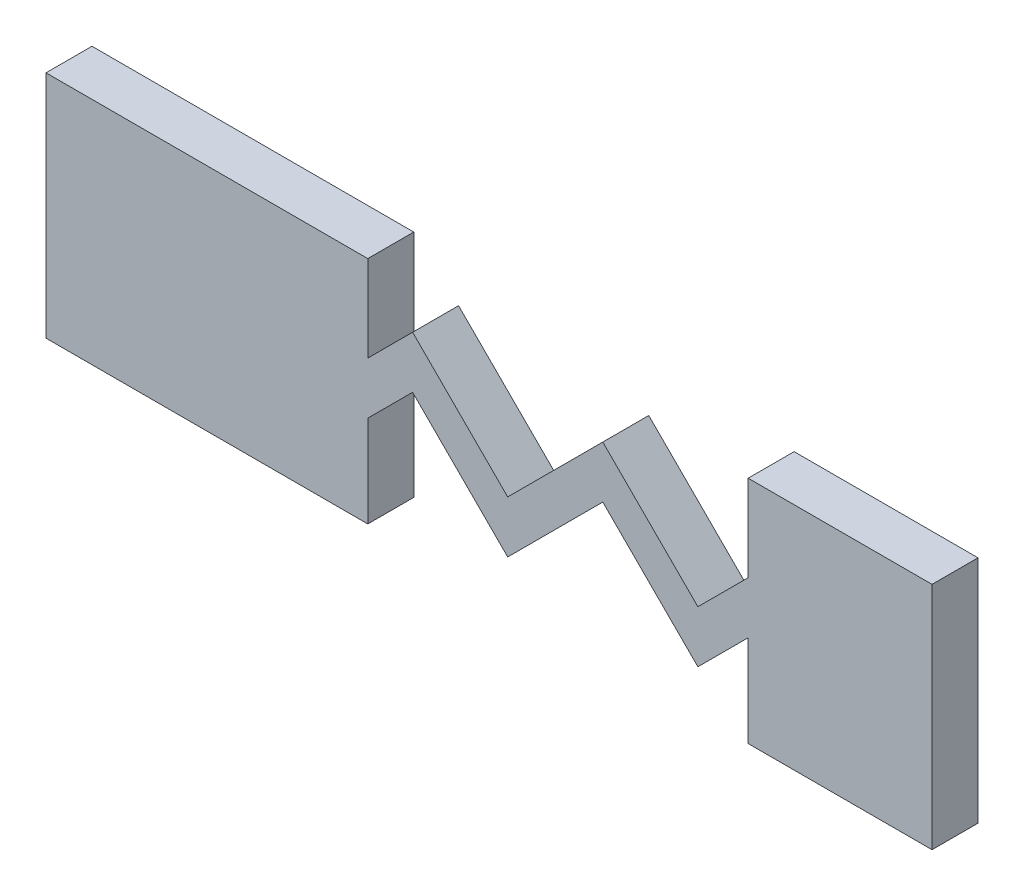
SolidWorks part; units mm, degrees
ref_plane "Front Plane" through (0, 0, 0) normal (0, 0, 1) x (1, 0, 0)
ref_plane "Top Plane" through (0, 0, 0) normal (0, 1, 0) x (1, 0, 0)
ref_plane "Right Plane" through (0, 0, 0) normal (1, 0, 0) x (0, 0, -1)
sketch "Sketch1" plane through (0, 0, 0) normal (0, 0, 1) x (1, 0, 0)
  line L0 (14, 6.25) -> (15.95, 8.2)
  line L1 (0, 0) -> (14, 0)
  line L2 (0, 0) -> (0, 10)
  line L3 (0, 10) -> (14, 10)
  line L4 (14, 0) -> (14, 10)
  line L5 (14, 6.25) -> (14, 3.9873)
  line L6 (15.95, 8.2) -> (15.95, 5.9373)
  line L7 (14, 3.9873) -> (15.95, 5.9373)
  line L9 (15.95, 8.2) -> (15.95, 5.9373)
  line L24 (14, 10) -> (-49986, 10) construction
  line L25 (15.95, 5.9373) -> (20.0873, 1.8)
  line L26 (15.95, 5.9373) -> (15.95, 8.2)
  line L31 (20.0873, 1.8) -> (20.0873, 4.0627)
  line L32 (15.95, 8.2) -> (20.0873, 4.0627)
  line L33 (15.95, 8.2) -> (-49984.05, 8.2) construction
  line L34 (20.3701, 1.8) -> (-49979.6299, 1.8) construction
  line L35 (20.0873, 4.0627) -> (15.95, 8.2)
  line L36 (20.0873, 4.0627) -> (20.0873, 1.8)
  line L37 (15.95, 8.2) -> (15.95, 5.9373)
  line L38 (20.0873, 1.8) -> (15.95, 5.9373)
  line L39 (20.0873, 4.0627) -> (24.2245, 8.2)
  line L40 (20.0873, 4.0627) -> (20.0873, 1.8)
  line L41 (24.2245, 8.2) -> (24.2245, 5.9373)
  line L42 (20.0873, 1.8) -> (24.2245, 5.9373)
  line L43 (24.2245, 5.9373) -> (28.3618, 1.8)
  line L44 (24.2245, 5.9373) -> (24.2245, 8.2)
  line L45 (28.3618, 1.8) -> (28.3618, 4.0627)
  line L46 (24.2245, 8.2) -> (28.3618, 4.0627)
  line L47 (28.3618, 4.0627) -> (30.549, 6.25)
  line L48 (28.3618, 4.0627) -> (28.3618, 1.8)
  line L49 (30.549, 6.25) -> (30.549, 3.9873)
  line L50 (28.3618, 1.8) -> (30.549, 3.9873)
  line L51 (14, 6.25) -> (-49986, 6.25) construction
  line L52 (14, 10) -> (-49986, 10) construction
  line L53 (13.7638, 0) -> (-49986.2362, 0) construction
  line L54 (30.549, 6.137) -> (30.549, -49993.863) construction
  line L56 (30.549, 10) -> (38.549, 10)
  line L57 (30.549, 10) -> (30.549, 0)
  line L58 (30.549, 0) -> (38.549, 0)
  line L59 (38.549, 10) -> (38.549, 0)
  dimension "D1" = 10
  dimension "D2" = 14
  dimension "D3" = 45
  dimension "D4" = 3.75
  dimension "D5" = 1.8
  dimension "D6" = 1.8
  dimension "D7" = 1.6
  dimension "D8" = 90
  dimension "D9" = 1.6
  dimension "D10" = 1.6
  dimension "D11" = 1.6
  dimension "D12" = 1.6
  dimension "D13" = 8
extrude "Boss-Extrude2" add sketch "Sketch1" along normal blind 2 contours L1 L4 L3 L2 | L4 L7 L6 L0 | L32 L6 L25 L31 | L31 L42 L41 L39 | L46 L41 L43 L45 | L45 L50 L49 L47 | L59 L56 L57 L49 L58 region at (14.975, 6.0936, 0) region at (7, 5, 0) region at (18.0186, 5, 0) region at (22.1559, 5, 0) region at (26.2931, 5, 0) region at (29.4554, 4.025, 0) region at (34.549, 5, 0)
